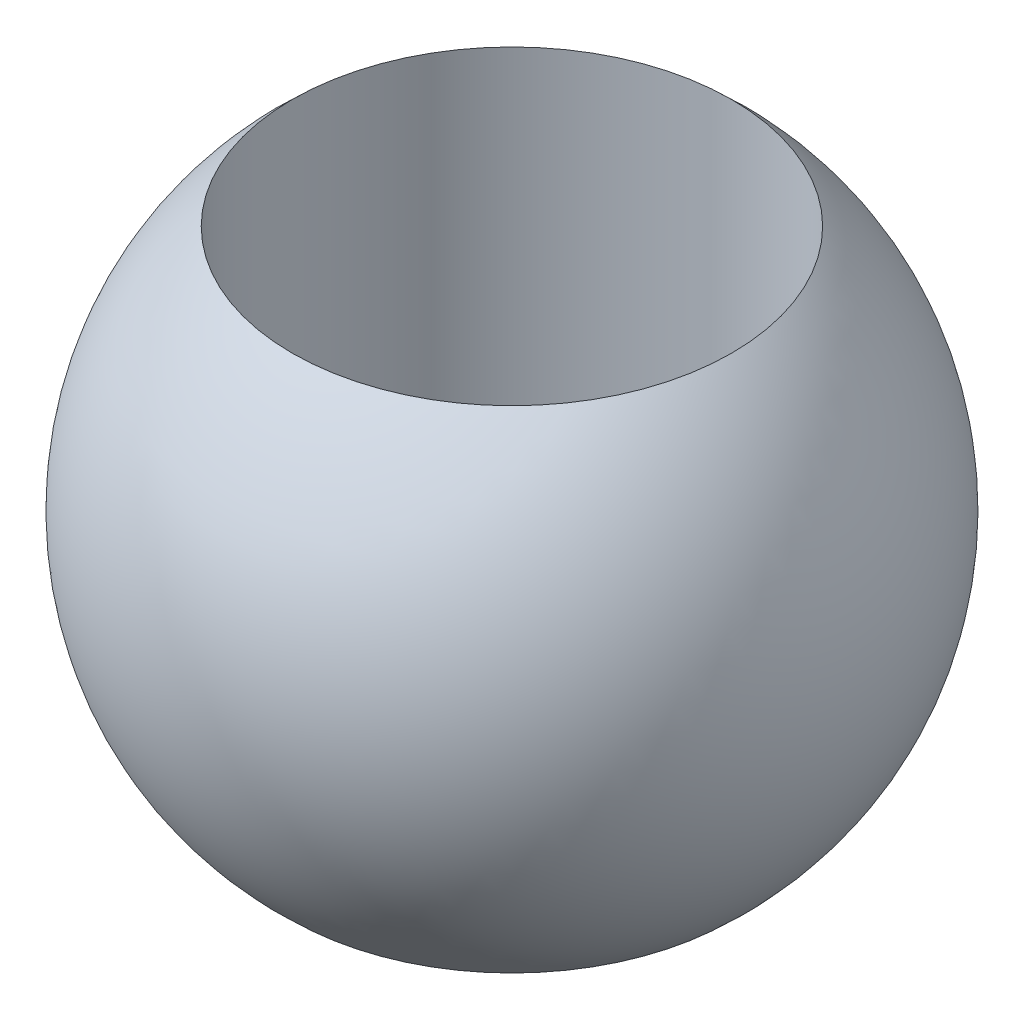
SolidWorks part; units mm, degrees
ref_plane "Front Plane" through (0, 0, 0) normal (0, 0, 1) x (1, 0, 0)
ref_plane "Top Plane" through (0, 0, 0) normal (0, 1, 0) x (1, 0, 0)
ref_plane "Right Plane" through (0, 0, 0) normal (1, 0, 0) x (0, 0, -1)
sketch "Sketch2" plane through (0, 0, 0) normal (0, 0, 1) x (1, 0, 0)
  line L0 (0, 3) -> (0, -3)
  arc A0 (0, -3) -> (0, 3) centre (0, 0) ccw
  dimension "D1" = 6
revolve "Revolve2" add sketch "Sketch2" angle 360 about L0
sketch "Sketch3" plane through (0, 0, 0) normal (0, 1, 0) x (1, 0, 0)
  circle A0 centre (0, 0) radius 2
  dimension "D1" = 4
extrude "Cut-Extrude1" cut sketch "Sketch3" against normal blind 10 and the other way blind 10
